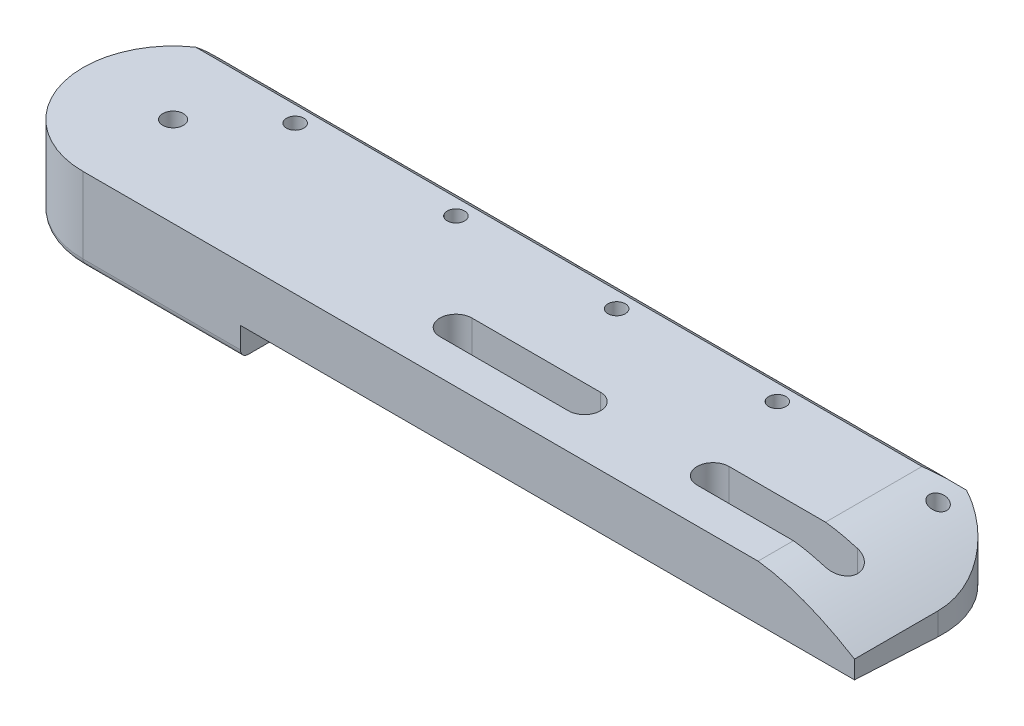
SolidWorks part; units mm, degrees
ref_plane "Front Plane" through (0, 0, 0) normal (0, 0, 1) x (1, 0, 0)
ref_plane "Top Plane" through (0, 0, 0) normal (0, 1, 0) x (1, 0, 0)
ref_plane "Right Plane" through (0, 0, 0) normal (1, 0, 0) x (0, 0, -1)
sketch "Sketch1" plane through (0, 0, 0) normal (0, 1, 0) x (1, 0, 0)
  line L0 (0, 3) -> (0, 2.4) construction
  line L2 (0, 14) -> (120, 14)
  line L7 (120, 14) -> (120, -14)
  line L8 (120, -14) -> (0, -14)
  line L9 (60, -14) -> (60, -6) construction
  line L10 (60, -6) -> (100, -6) construction
  line L11 (70, -6) -> (50, -6) construction
  line L13 (70, -8.5) -> (50, -8.5)
  line L14 (70, -3.5) -> (50, -3.5)
  line L15 (90, -6) -> (110, -6) construction
  line L16 (90, -3.5) -> (110, -3.5)
  line L17 (90, -8.5) -> (110, -8.5)
  line L20 (60, 14) -> (60, 9) construction
  line L21 (60, 9) -> (110, 9) construction
  arc A1 (0, 14) -> (0, -14) centre (0, 0) ccw
  arc A2 (70, -8.5) -> (70, -3.5) centre (70, -6) ccw
  arc A3 (50, -3.5) -> (50, -8.5) centre (50, -6) ccw
  arc A4 (90, -3.5) -> (90, -8.5) centre (90, -6) ccw
  arc A5 (110, -8.5) -> (110, -3.5) centre (110, -6) ccw
  circle A8 centre (85, 9) radius 1.35
  circle A9 centre (60, 9) radius 1.35
  circle A10 centre (110, 9) radius 1.35
  circle A11 centre (10, 9) radius 1.35
  circle A12 centre (35, 9) radius 1.35
  circle A13 centre (0, 0) radius 3
  point P9 (0, 2.4)
  point P18 (60, -6)
  point P25 (100, -6)
  dimension "D1" = 28
  dimension "D3" = 0.6
  dimension "D4" = 3
  dimension "D5" = 120
  dimension "D6" = 28
  dimension "D7" = 8
  dimension "D8" = 5
  dimension "D9" = 50
extrude "Boss-Extrude1" add sketch "Sketch1" along normal blind 10
sketch "Sketch9" plane through (0, 10, 0) normal (0, 1, 0) x (1, 0, 0)
  line L0 (0, -14) -> (120, -14) construction
  line L1 (0, 14) -> (24.5, 14)
  line L3 (0, -14) -> (24.5, -14)
  line L4 (24.5, 14) -> (24.5, -14)
  circle A0 centre (0, 0) radius 3
  arc A1 (0, 14) -> (0, -14) centre (0, 0) ccw
  dimension "D1" = 24.5
extrude "Boss-Extrude2" add sketch "Sketch9" along normal blind 3
sketch "Sketch10" plane through (0, 13, 0) normal (0, 1, 0) x (1, 0, 0)
  line L5 (0, 3) -> (38, 3)
  line L6 (0, 3) -> (0, -3)
  line L7 (0, -3) -> (38, -3)
  line L8 (38, 3) -> (38, -3)
  circle A1 centre (0, 0) radius 3 construction
  dimension "D1" = 38
  dimension "D2" = 6
extrude "Cut-Extrude3" cut sketch "Sketch10" against normal blind 8
sketch "Sketch4" plane through (120, 0, 0) normal (1, 0, 0) x (0, 0, -1)
  line L0 (-14, 10) -> (-14, 8.5)
  line L1 (-14, 10) -> (-14, 0) construction
  line L3 (-14, 10) -> (14, 10)
  line L4 (-14, 8.5) -> (14, 10)
  dimension "D1" = 1.5
fillet "Fillet3" radius 15 1 edges at (120, 5, -14)
fillet "Fillet4" radius 1.2 2 edges at (19, 5, 3) (19, 5, -3)
extrude "Cut-Extrude4" cut sketch "Sketch4" against normal up to surface (95.5 mm away) up to face at (24.5, 11.5, 8.5)
sketch "Sketch11" plane through (0, 0, -14) normal (0, 0, -1) x (-1, 0, 0)
  line L0 (-120, 9.1964) -> (-120, 5.6964)
  line L1 (-120, 0) -> (-120, 9.1964) construction
  line L2 (-120, 5.6964) -> (-120, 0)
  line L3 (-120, 0) -> (-105, 0)
  spline S0 degree 2 poles (-120, 5.6964) (-112.0758, 0.8452) (-105, 0) knots 0 0 0 0.273587 0.273587 0.273587
  dimension "D1" = 3.5
extrude "Cut-Extrude5" cut sketch "Sketch11" against normal blind 56 contours S0 L2 L3 region at (115.7103, 1.748, -14)
sketch "Sketch13" plane through (0, 0, 0) normal (0, -1, 0) x (1, 0, 0)
  circle A0 centre (0, 0) radius 3
  circle A1 centre (0, 0) radius 1.6
  dimension "D1" = 3.2
extrude "Boss-Extrude3" add sketch "Sketch13" against normal up to surface (5 mm away) up to face at (20.35, 5, 0)
fillet "Fillet5" radius 1.2 3 edges at (12.25, 13, -14) (-14, 13, 0) (12.25, 13, 14)
sketch "Sketch14" plane through (120, 0, 0) normal (1, 0, 0) x (0, 0, -1)
  line L0 (14, 0) -> (11.5, 0)
  line L1 (-3.5, 0) -> (14, 0) construction
  line L2 (14, 0) -> (14, 3)
  line L3 (14, 10) -> (14, 0) construction
  spline S0 degree 2 poles (11.5, 0) (13.1013, 0.7826) (14, 3) knots 0 0 0 0.269081 0.269081 0.269081
  dimension "D1" = 3
  dimension "D2" = 2.5
extrude "Cut-Extrude6" cut sketch "Sketch14" against normal blind 160.5
mirror "Mirror1" about plane through (0, 13, 0) normal (0, 1, 0) of bodies 112
sketch "Sketch15" plane through (0, 0, 0) normal (0, -1, 0) x (1, 0, 0)
  line L1 (120, 14) -> (-26.1406, 14)
  line L2 (120, 14) -> (120, -24.948)
  line L3 (120, -24.948) -> (-26.1406, -24.948)
  line L4 (-26.1406, 14) -> (-26.1406, -24.948)
extrude "Cut-Extrude7" cut sketch "Sketch15" against normal blind 13
